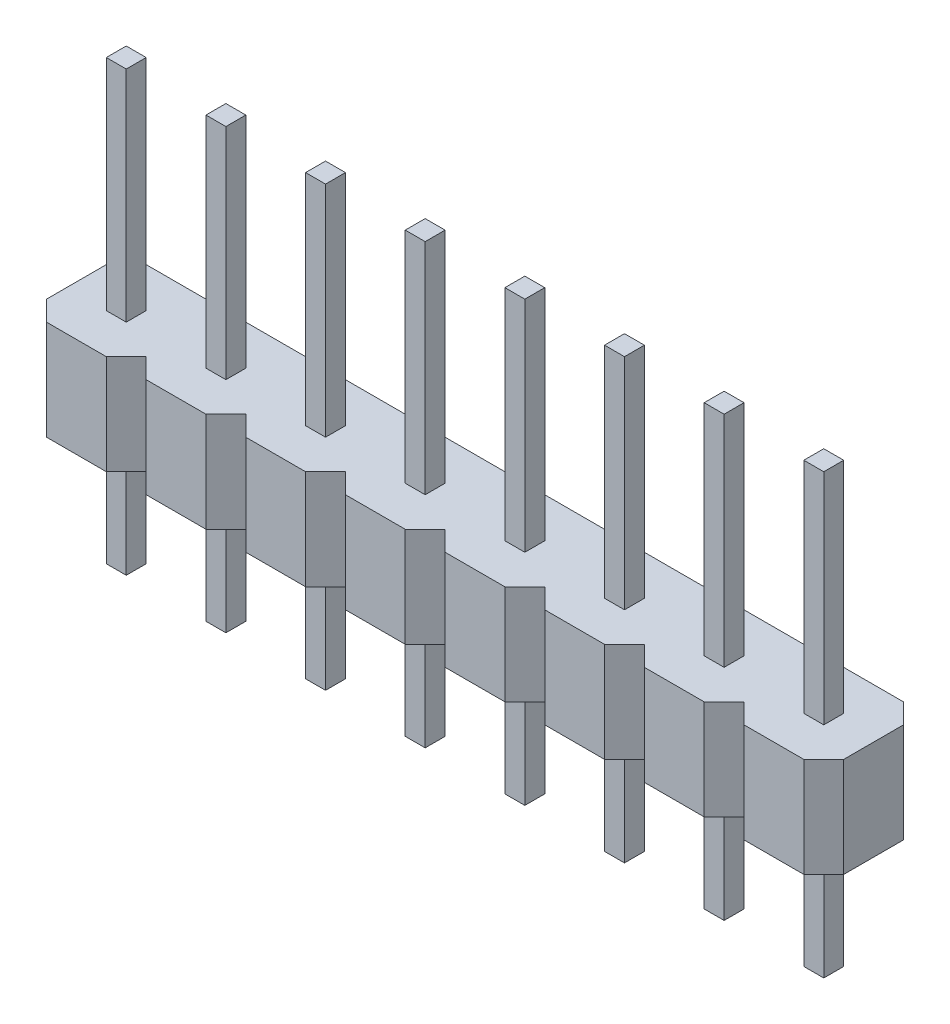
SolidWorks part; units mm, degrees
ref_plane "Front Plane" through (0, 0, 0) normal (0, 0, 1) x (1, 0, 0)
ref_plane "Top Plane" through (0, 0, 0) normal (0, 1, 0) x (1, 0, 0)
ref_plane "Right Plane" through (0, 0, 0) normal (1, 0, 0) x (0, 0, -1)
sketch "Sketch1" plane through (0, 0, 0) normal (0, 1, 0) x (1, 0, 0)
  line L0 (-1.25, 0.75) -> (-0.75, 1.25)
  line L1 (-0.75, -1.25) -> (0.75, -1.25)
  line L2 (-1.25, -0.75) -> (-1.25, 0.75)
  line L3 (-0.75, 1.25) -> (0.75, 1.25)
  line L5 (-1.25, -1.25) -> (1.25, 1.25) construction
  line L6 (-1.25, 1.25) -> (1.25, -1.25) construction
  line L7 (0.75, 1.25) -> (1.25, 0.75)
  line L8 (0.75, -1.25) -> (1.25, -0.75)
  line L9 (-1.25, -0.75) -> (-0.75, -1.25)
  line L11 (1.75, 1.25) -> (3.25, 1.25)
  line L12 (3.25, 1.25) -> (3.75, 0.75)
  line L13 (1.25, 0.75) -> (1.75, 1.25)
  line L15 (1.25, -0.75) -> (1.75, -1.25)
  line L16 (1.75, -1.25) -> (3.25, -1.25)
  line L17 (3.25, -1.25) -> (3.75, -0.75)
  line L18 (1.25, 1.25) -> (3.75, -1.25) construction
  line L19 (1.25, -1.25) -> (3.75, 1.25) construction
  line L21 (4.25, 1.25) -> (5.75, 1.25)
  line L22 (5.75, 1.25) -> (6.25, 0.75)
  line L23 (3.75, 0.75) -> (4.25, 1.25)
  line L25 (3.75, -0.75) -> (4.25, -1.25)
  line L26 (4.25, -1.25) -> (5.75, -1.25)
  line L27 (5.75, -1.25) -> (6.25, -0.75)
  line L28 (3.75, 1.25) -> (6.25, -1.25) construction
  line L29 (3.75, -1.25) -> (6.25, 1.25) construction
  line L31 (6.75, 1.25) -> (8.25, 1.25)
  line L32 (8.25, 1.25) -> (8.75, 0.75)
  line L33 (6.25, 0.75) -> (6.75, 1.25)
  line L35 (6.25, -0.75) -> (6.75, -1.25)
  line L36 (6.75, -1.25) -> (8.25, -1.25)
  line L37 (8.25, -1.25) -> (8.75, -0.75)
  line L38 (6.25, 1.25) -> (8.75, -1.25) construction
  line L39 (6.25, -1.25) -> (8.75, 1.25) construction
  line L41 (9.25, 1.25) -> (10.75, 1.25)
  line L42 (10.75, 1.25) -> (11.25, 0.75)
  line L43 (8.75, 0.75) -> (9.25, 1.25)
  line L45 (8.75, -0.75) -> (9.25, -1.25)
  line L46 (9.25, -1.25) -> (10.75, -1.25)
  line L47 (10.75, -1.25) -> (11.25, -0.75)
  line L48 (8.75, 1.25) -> (11.25, -1.25) construction
  line L49 (8.75, -1.25) -> (11.25, 1.25) construction
  line L51 (11.75, 1.25) -> (13.25, 1.25)
  line L52 (13.25, 1.25) -> (13.75, 0.75)
  line L53 (11.25, 0.75) -> (11.75, 1.25)
  line L55 (11.25, -0.75) -> (11.75, -1.25)
  line L56 (11.75, -1.25) -> (13.25, -1.25)
  line L57 (13.25, -1.25) -> (13.75, -0.75)
  line L58 (11.25, 1.25) -> (13.75, -1.25) construction
  line L59 (11.25, -1.25) -> (13.75, 1.25) construction
  line L61 (14.25, 1.25) -> (15.75, 1.25)
  line L62 (15.75, 1.25) -> (16.25, 0.75)
  line L63 (13.75, 0.75) -> (14.25, 1.25)
  line L65 (13.75, -0.75) -> (14.25, -1.25)
  line L66 (14.25, -1.25) -> (15.75, -1.25)
  line L67 (15.75, -1.25) -> (16.25, -0.75)
  line L68 (13.75, 1.25) -> (16.25, -1.25) construction
  line L69 (13.75, -1.25) -> (16.25, 1.25) construction
  line L70 (18.75, -0.75) -> (18.75, 0.75)
  line L71 (16.75, 1.25) -> (18.25, 1.25)
  line L72 (18.25, 1.25) -> (18.75, 0.75)
  line L73 (16.25, 0.75) -> (16.75, 1.25)
  line L75 (16.25, -0.75) -> (16.75, -1.25)
  line L76 (16.75, -1.25) -> (18.25, -1.25)
  line L77 (18.25, -1.25) -> (18.75, -0.75)
  line L78 (16.25, 1.25) -> (18.75, -1.25) construction
  line L79 (16.25, -1.25) -> (18.75, 1.25) construction
  line L80 (1.25, -0.75) -> (1.25, 0.75) [skipped]
  line L81 (3.75, -0.75) -> (3.75, 0.75) [skipped]
  line L82 (6.25, -0.75) -> (6.25, -0.032) [skipped]
  line L83 (8.75, -0.75) -> (8.75, 0.75) [skipped]
  line L84 (11.25, -0.75) -> (11.25, 0.75) [skipped]
  line L85 (13.75, -0.75) -> (13.75, 0.75) [skipped]
  line L86 (16.25, -0.75) -> (16.25, 0.75) [skipped]
  point P0 (0, 0)
  point P18 (18.75, -0.75)
  point P19 (0, 0)
  point P26 (0, 0)
  dimension "D1" = 2.5
  dimension "D2" = 2.5
  dimension "D3" = 8
extrude "Boss-Extrude1" add sketch "Sketch1" along normal blind 2.5
sketch "Sketch2" plane through (0, 2.5, 0) normal (0, 1, 0) x (1, 0, 0)
  line L0 (2.25, 0.25) -> (2.75, 0.25)
  line L1 (-0.25, -0.25) -> (0.25, -0.25)
  line L2 (-0.25, -0.25) -> (-0.25, 0.25)
  line L3 (-0.25, 0.25) -> (0.25, 0.25)
  line L4 (0.25, -0.25) -> (0.25, 0.25)
  line L5 (-0.25, -0.25) -> (0.25, 0.25) construction
  line L6 (-0.25, 0.25) -> (0.25, -0.25) construction
  line L7 (2.75, -0.25) -> (2.75, 0.25)
  line L8 (2.25, 0.25) -> (2.75, -0.25) construction
  line L9 (2.25, -0.25) -> (2.75, -0.25)
  line L10 (2.25, -0.25) -> (2.75, 0.25) construction
  line L11 (2.25, -0.25) -> (2.25, 0.25)
  line L12 (4.75, 0.25) -> (5.25, 0.25)
  line L13 (5.25, -0.25) -> (5.25, 0.25)
  line L14 (4.75, 0.25) -> (5.25, -0.25) construction
  line L15 (4.75, -0.25) -> (5.25, -0.25)
  line L16 (4.75, -0.25) -> (5.25, 0.25) construction
  line L17 (4.75, -0.25) -> (4.75, 0.25)
  line L18 (7.25, 0.25) -> (7.75, 0.25)
  line L19 (7.75, -0.25) -> (7.75, 0.25)
  line L20 (7.25, 0.25) -> (7.75, -0.25) construction
  line L21 (7.25, -0.25) -> (7.75, -0.25)
  line L22 (7.25, -0.25) -> (7.75, 0.25) construction
  line L23 (7.25, -0.25) -> (7.25, 0.25)
  line L24 (9.75, 0.25) -> (10.25, 0.25)
  line L25 (10.25, -0.25) -> (10.25, 0.25)
  line L26 (9.75, 0.25) -> (10.25, -0.25) construction
  line L27 (9.75, -0.25) -> (10.25, -0.25)
  line L28 (9.75, -0.25) -> (10.25, 0.25) construction
  line L29 (9.75, -0.25) -> (9.75, 0.25)
  line L30 (12.25, 0.25) -> (12.75, 0.25)
  line L31 (12.75, -0.25) -> (12.75, 0.25)
  line L32 (12.25, 0.25) -> (12.75, -0.25) construction
  line L33 (12.25, -0.25) -> (12.75, -0.25)
  line L34 (12.25, -0.25) -> (12.75, 0.25) construction
  line L35 (12.25, -0.25) -> (12.25, 0.25)
  line L36 (14.75, 0.25) -> (15.25, 0.25)
  line L37 (15.25, -0.25) -> (15.25, 0.25)
  line L38 (14.75, 0.25) -> (15.25, -0.25) construction
  line L39 (14.75, -0.25) -> (15.25, -0.25)
  line L40 (14.75, -0.25) -> (15.25, 0.25) construction
  line L41 (14.75, -0.25) -> (14.75, 0.25)
  line L42 (17.25, 0.25) -> (17.75, 0.25)
  line L43 (17.75, -0.25) -> (17.75, 0.25)
  line L44 (17.25, 0.25) -> (17.75, -0.25) construction
  line L45 (17.25, -0.25) -> (17.75, -0.25)
  line L46 (17.25, -0.25) -> (17.75, 0.25) construction
  line L47 (17.25, -0.25) -> (17.25, 0.25)
  point P0 (0, 0)
  point P5 (2.5, 0)
  dimension "D1" = 0.5
  dimension "D2" = 0.5
  dimension "D4" = 2.5
  dimension "D3" = 8
extrude "Boss-Extrude2" add sketch "Sketch2" along normal blind 5.5
extrude "Boss-Extrude3" add sketch "Sketch2<2>" against normal blind 5.5
sketch "Sketch2<2>" plane through (0, 2.5, 0) normal (0, 1, 0) x (1, 0, 0) same geometry as "Sketch2"
